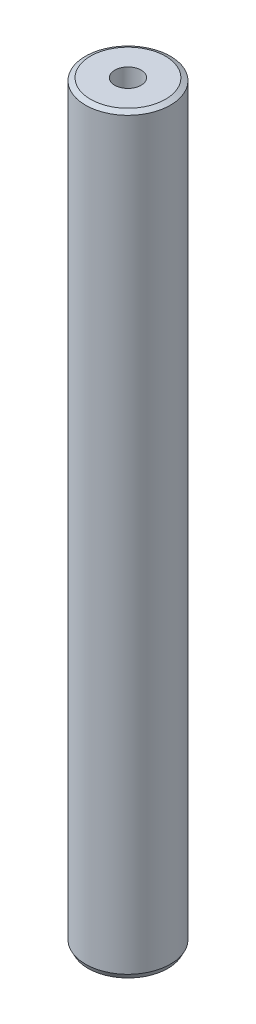
SolidWorks part; units mm, degrees
ref_plane "Front Plane" through (0, 0, 0) normal (0, 0, 1) x (1, 0, 0)
ref_plane "Top Plane" through (0, 0, 0) normal (0, 1, 0) x (1, 0, 0)
ref_plane "Right Plane" through (0, 0, 0) normal (1, 0, 0) x (0, 0, -1)
sketch "Sketch1" plane through (0, 0, 0) normal (0, 1, 0) x (1, 0, 0)
  circle A0 centre (0, 0) radius 5
  dimension "SHAFT_OD" = 10
extrude "Boss-Extrude1" add sketch "Sketch1" along normal blind 88.4913
sketch "Sketch2" plane through (0, 0, 0) normal (0, 1, 0) x (1, 0, 0)
  circle A0 centre (0, 0) radius 1.552
  dimension "BORE_D" = 3.104
extrude "Cut-Extrude1" cut sketch "Sketch2" along normal through all
chamfer "Chamfer1" distance 0.3019 angle 62.922 2 edges at (0, 88.4913, 5) (0, 0, 5) first distance on face at (0, 88.4913, 5) first distance on face at (0, 0, 1.552)
